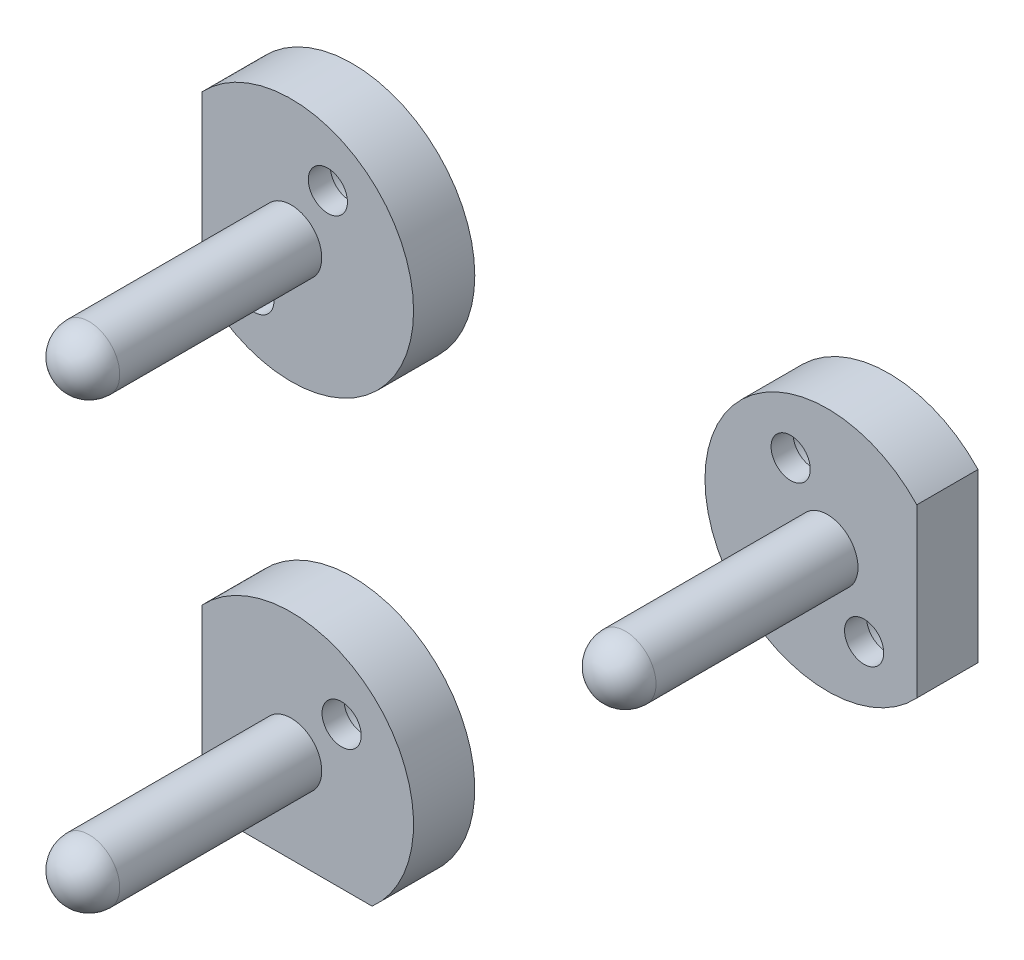
SolidWorks part; units mm, degrees
ref_plane "前基準面" through (0, 0, 0) normal (0, 0, 1) x (1, 0, 0)
ref_plane "上基準面" through (0, 0, 0) normal (0, 1, 0) x (1, 0, 0)
ref_plane "右基準面" through (0, 0, 0) normal (1, 0, 0) x (0, 0, -1)
sketch "草圖1" plane through (0, 0, 0) normal (0, 0, 1) x (1, 0, 0)
  line L0 (0, 26.9) -> (0, -26.9) construction
  line L1 (-34.9, 26.9) -> (34.9, 26.9) construction
  line L2 (-34.9, 26.9) -> (-34.9, -26.9) construction
  line L3 (-34.9, -26.9) -> (34.9, -26.9) construction
  line L4 (34.9, 26.9) -> (34.9, -26.9) construction
  line L5 (-34.9, 26.9) -> (34.9, -26.9) construction
  line L6 (-34.9, -26.9) -> (34.9, 26.9) construction
  circle A0 centre (-21.9, 16.9) radius 10
  circle A1 centre (-21.9, -19.4) radius 10
  circle A2 centre (21.9, 16.9) radius 10
  point P0 (0, 0)
  dimension "D5" = 20
  dimension "D6" = 20
  dimension "D1" = 69.8
  dimension "D2" = 53.8
  dimension "D3" = 10
  dimension "D4" = 13
  dimension "D7" = 7.5
extrude "填料-伸長1" add sketch "草圖1" along normal blind 5
sketch "草圖2" plane through (0, 0, 5) normal (0, 0, 1) x (1, 0, 0)
  circle A0 centre (-21.9, 16.9) radius 2.5
  circle A1 centre (21.9, 16.9) radius 2.5
  circle A2 centre (-21.9, -19.4) radius 2.5
  dimension "D1" = 5
  dimension "D2" = 5
  dimension "D3" = 5
extrude "填料-伸長2" add sketch "草圖2" along normal blind 19
ref_plane "平面1" through (-24.9, 0, 0) normal (1, 0, 0) x (0, 0, -1)
fillet "圓角4" radius 2.5 1 edges at (-19.4, 16.9, 24)
fillet "圓角5" radius 2.5 1 edges at (-19.4, -19.4, 24)
fillet "圓角6" radius 2.5 1 edges at (24.4, 16.9, 24)
sketch "草圖4" plane through (0, 0, 0) normal (0, 0, -1) x (-1, 0, 0)
  line L0 (31.9, -19.4) -> (11.9, -19.4) construction
  line L1 (21.9, -19.4) -> (21.9, 16.9) construction
  line L2 (15.2856, -26.9) -> (28.5144, -26.9)
  line L3 (29.2, -12.5655) -> (29.2, -26.2345)
  line L4 (29.2, 23.7345) -> (29.2, 10.0655)
  line L5 (-21.9, 26.9) -> (-21.9, 6.9) construction
  line L6 (-29.2, 23.7345) -> (-29.2, 10.0655)
  circle A0 centre (21.9, -19.4) radius 10 construction
  arc A1 (28.5144, -26.9) -> (15.2856, -26.9) centre (21.9, -19.4) cw
  arc A2 (29.2, -12.5655) -> (29.2, -26.2345) centre (21.9, -19.4) cw
  circle A3 centre (21.9, 16.9) radius 10 construction
  arc A4 (29.2, 23.7345) -> (29.2, 10.0655) centre (21.9, 16.9) cw
  circle A5 centre (-21.9, 16.9) radius 10 construction
  arc A6 (-29.2, 23.7345) -> (-29.2, 10.0655) centre (-21.9, 16.9) ccw
  point P8 (21.9, -19.4)
  circle M3 centre (21.9, -19.4) radius 10
  dimension "D1" = 7.5
  dimension "D2" = 7.3
  dimension "D3" = 7.3
extrude "除料-伸長1" cut sketch "草圖4" against normal blind 10 contours L2 M3 | A6 L6 | A4 L4 | A2 L3 region at (-21.9, -27.9116, 0)
sketch "草圖5" plane through (0, 0, 0) normal (0, 0, -1) x (-1, 0, 0)
  line L0 (-21.9, 16.9) -> (21.9, 16.9) construction
  line L1 (21.9, 16.9) -> (21.9, -19.4) construction
  line L2 (0, 29.5747) -> (0, -30.7013) construction
  line L3 (17.7769, -15.2769) -> (26.0231, -23.5231) construction
  circle A0 centre (-18.9, 21.9) radius 2.85
  circle A1 centre (26.0231, -23.5231) radius 2.85
  circle A2 centre (-24.9, 11.9) radius 2.85
  circle A3 centre (-21.9, 16.9) radius 2.5 construction
  circle A4 centre (24.9, 11.9) radius 2.85
  circle A5 centre (18.9, 21.9) radius 2.85
  circle A6 centre (17.7769, -15.2769) radius 2.85
  dimension "D1" = 5.7
  dimension "D5" = 5.7
  dimension "D8" = 5
  dimension "D10" = 5.7
  dimension "D11" = 5.7
  dimension "D2" = 45
  dimension "D3" = 5
  dimension "D4" = 3
  dimension "D6" = 5
  dimension "D7" = 3
  dimension "D9" = 11.6619
extrude "除料-伸長2" cut sketch "草圖5" against normal blind 3.2
sketch "草圖6" plane through (0, 0, 3.2) normal (0, 0, -1) x (-1, 0, 0)
  circle A0 centre (-18.9, 21.9) radius 1.6
  circle A1 centre (-24.9, 11.9) radius 1.6
  circle A2 centre (18.9, 21.9) radius 1.6
  circle A3 centre (24.9, 11.9) radius 1.6
  circle A4 centre (17.7769, -15.2769) radius 1.6
  circle A5 centre (26.0231, -23.5231) radius 1.6
  dimension "D1" = 3.2
  dimension "D2" = 3.2
  dimension "D3" = 3.2
  dimension "D4" = 3.2
  dimension "D5" = 3.2
  dimension "D6" = 3.2
extrude "除料-伸長3" cut sketch "草圖6" against normal up to next
